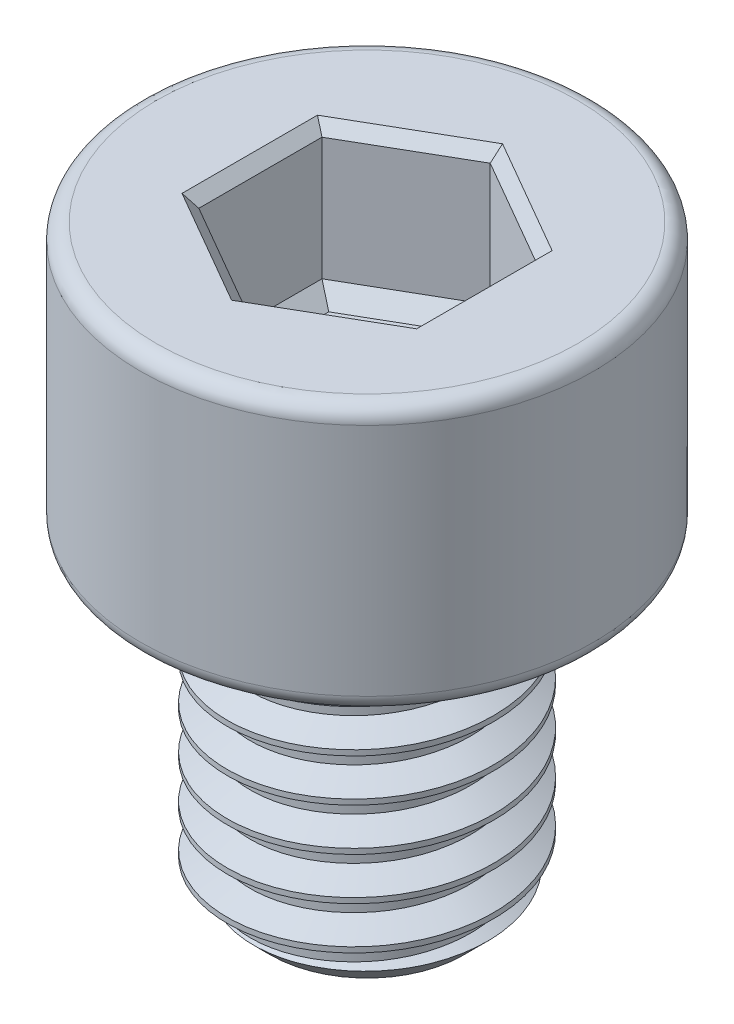
SolidWorks part; units mm, degrees
material "AISI Type A2 Tool Steel"
ref_plane "Front Plane" through (0, 0, 0) normal (0, 0, 1) x (1, 0, 0)
ref_plane "Top Plane" through (0, 0, 0) normal (0, 1, 0) x (1, 0, 0)
ref_plane "Right Plane" through (0, 0, 0) normal (1, 0, 0) x (0, 0, -1)
sketch "Sketch1" plane through (0, 0, 0) normal (0, 1, 0) x (1, 0, 0)
  circle A0 centre (0, 0) radius 2.5
  dimension "D1" = 5
extrude "Boss-Extrude1" add sketch "Sketch1" along normal blind 6
thread "Thread1" pitch 0.8 method cut profile "Thread Profile1" start angle 0, offset 1, length 0, pitch 0.8, diameter 5
ref_plane "Plane1" through (-2.5, 7, 0) normal (0, 0, 1) x (-1, 0, 0)
sketch "Thread Profile1" plane through (-2.5, 7, 0) normal (0, 0, 1) x (-1, 0, 0)
  line L0 (0, 0) -> (0, 0.8) construction
  line L11 (0, 0) -> (0, 0.7)
  line L12 (0, 0.7) -> (-0.433, 0.45)
  line L13 (-0.433, 0.45) -> (-0.433, 0.25)
  line L15 (-0.433, 0.25) -> (0, 0)
  line L17 (-0.433, 0.35) -> (0, 0.35) construction
  point P2 (0, 0)
  dimension "Pitch" = 0.8
  dimension "Profile_Angle" = 60
  dimension "Profile_Land" = 0.2
  dimension "Profile_Height" = 0.433
sketch "Sketch5" plane through (0, 6, 0) normal (0, 1, 0) x (1, 0, 0)
  circle A0 centre (0, 0) radius 4.25
  dimension "D1" = 8.5
extrude "Boss-Extrude2" add sketch "Sketch5" along normal blind 5
fillet "Fillet1" radius 0.3 2 edges at (0, 6, 4.25) (0, 11, 4.25)
sketch "Sketch6" plane through (0, 0, 0) normal (0, 0, 1) x (1, 0, 0)
  line L0 (0, 0) -> (0, 0.2882) construction
  line L1 (0, 0) -> (2.51, 0) construction
  line L2 (2.51, 0) -> (2.51, 0.7)
  line L3 (2.51, 0.7) -> (1.81, 0)
  line L4 (1.81, 0) -> (2.51, 0)
  dimension "D1" = 45
  dimension "D2" = 0.7
  dimension "D3" = 2.51
revolve "Cut-Revolve1" cut sketch "Sketch6" angle 360 about L0
sketch "Sketch7" plane through (0, 11, 0) normal (0, 1, 0) x (1, 0, 0)
  line L1 (0, 2.3094) -> (-2, 1.1547)
  line L2 (-2, 1.1547) -> (-2, -1.1547)
  line L3 (-2, -1.1547) -> (0, -2.3094)
  line L4 (0, -2.3094) -> (2, -1.1547)
  line L5 (2, -1.1547) -> (2, 1.1547)
  line L6 (2, 1.1547) -> (0, 2.3094)
  circle A0 centre (0, 0) radius 2 construction
  dimension "D1" = 4
extrude "Cut-Extrude1" cut sketch "Sketch7" against normal blind 2.5
chamfer "Chamfer1" distance 0.2 angle 45 6 edges at (-2, 11, 0) (-1, 11, 1.7321) (1, 11, 1.7321) (2, 11, 0) (1, 11, -1.7321) (-1, 11, -1.7321)
sketch "Sketch8" plane through (0, 8.5, 0) normal (0, 1, 0) x (1, 0, 0)
  line L1 (0, 2.3094) -> (-2, 1.1547)
  line L2 (-2, 1.1547) -> (-2, -1.1547)
  line L3 (-2, -1.1547) -> (0, -2.3094)
  line L4 (0, -2.3094) -> (2, -1.1547)
  line L5 (2, -1.1547) -> (2, 1.1547)
  line L6 (2, 1.1547) -> (0, 2.3094)
  circle A0 centre (0, 0) radius 2 construction
extrude "Cut-Extrude2" cut sketch "Sketch8" against normal blind 0.3 draft 45
